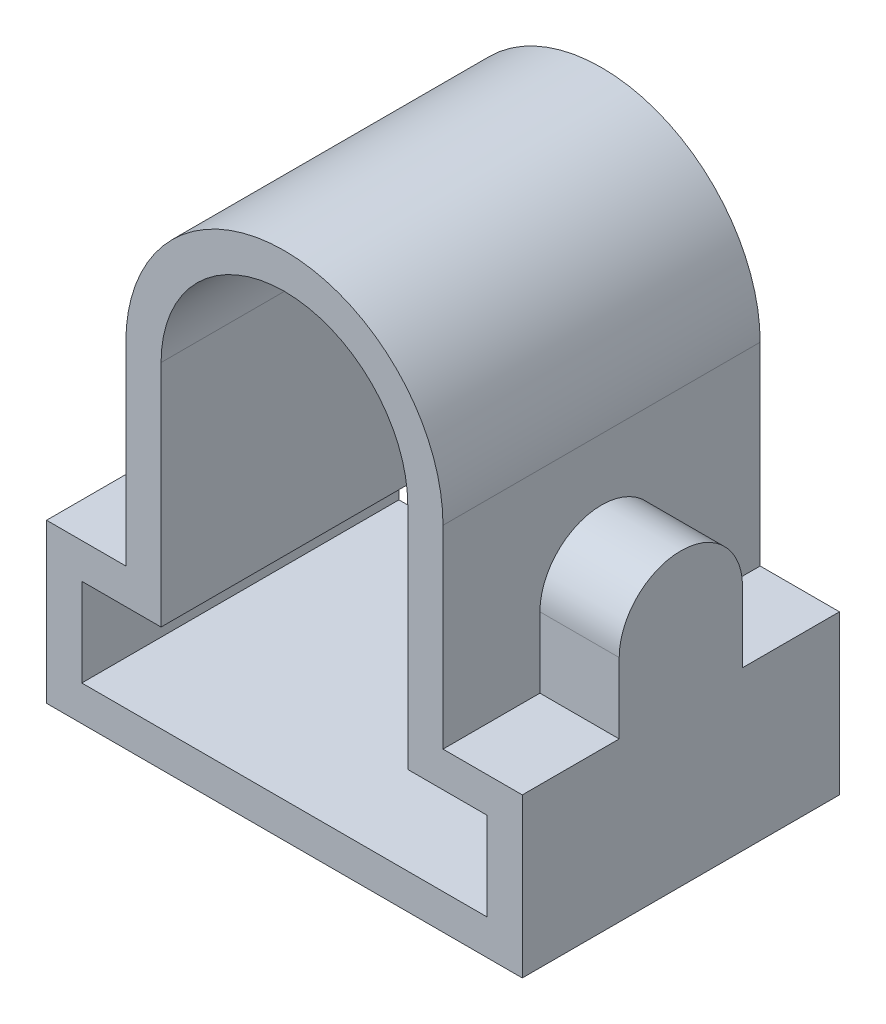
SolidWorks part; units mm, degrees
ref_plane "Front Plane" through (0, 0, 0) normal (0, 0, 1) x (1, 0, 0)
ref_plane "Top Plane" through (0, 0, 0) normal (0, 1, 0) x (1, 0, 0)
ref_plane "Right Plane" through (0, 0, 0) normal (1, 0, 0) x (0, 0, -1)
sketch "Sketch1" plane through (0, 0, 0) normal (0, 0, 1) x (1, 0, 0)
  line L0 (-67.5, 0) -> (67.5, 0)
  line L1 (67.5, 0) -> (67.5, 45)
  line L2 (67.5, 45) -> (45, 45)
  line L3 (45, 45) -> (45, 100)
  line L4 (0, -24.2865) -> (0, 78.6055) construction
  line L5 (-67.5, 0) -> (-67.5, 45)
  line L6 (-67.5, 45) -> (-45, 45)
  line L7 (-45, 45) -> (-45, 100)
  line L8 (-35, 35) -> (-35, 100)
  line L9 (-57.5, 35) -> (-35, 35)
  line L10 (-57.5, 10) -> (-57.5, 35)
  line L11 (-57.5, 10) -> (57.5, 10)
  line L12 (57.5, 10) -> (57.5, 35)
  line L13 (57.5, 35) -> (35, 35)
  line L14 (35, 35) -> (35, 100)
  arc A0 (45, 100) -> (-45, 100) centre (0, 100) ccw
  arc A1 (35, 100) -> (-35, 100) centre (0, 100) ccw
  point P3 (-66.1685, 0)
  point P4 (0, 0)
  dimension "D1" = 45
  dimension "D2" = 45
  dimension "D3" = 135
  dimension "D4" = 100
  dimension "D5" = 10
extrude "Boss-Extrude1" add sketch "Sketch1" along normal blind 45 and the other way blind 45
sketch "Sketch2" plane through (45, 0, 0) normal (1, 0, 0) x (0, 0, -1)
  line L0 (-45, 0) -> (-45, 45) construction
  line L1 (17.5, 65) -> (17.5, 45)
  line L2 (45, 45) -> (-45, 45) construction
  line L3 (-17.5, 65) -> (-17.5, 45)
  line L4 (-17.5, 45) -> (17.5, 45)
  arc A0 (17.5, 65) -> (-17.5, 65) centre (0, 65) ccw
  dimension "D1" = 65
  dimension "D2" = 45
extrude "Boss-Extrude2" add sketch "Sketch2" along normal up to vertex (22.5 mm away) up to point (67.5, 45, 45)
